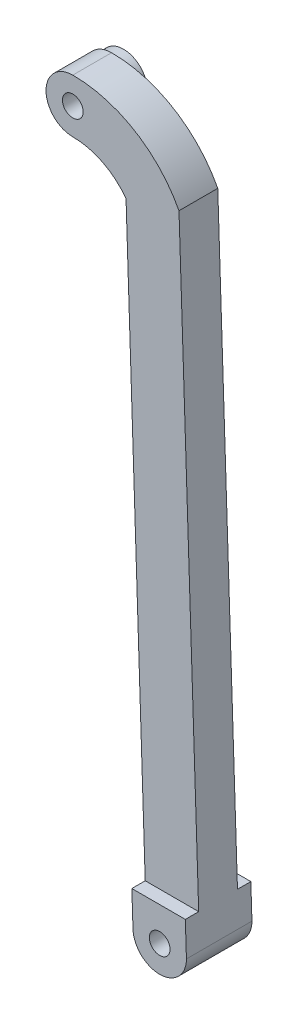
SolidWorks part; units mm, degrees
ref_plane "Plan de face" through (0, 0, 0) normal (0, 0, 1) x (1, 0, 0)
ref_plane "Plan de dessus" through (0, 0, 0) normal (0, 1, 0) x (1, 0, 0)
ref_plane "Plan de droite" through (0, 0, 0) normal (1, 0, 0) x (0, 0, -1)
sketch "Esquisse1" plane through (0, 0, 0) normal (0, 0, 1) x (1, 0, 0)
  line L2 (0, 0) -> (0, 100) construction
  line L3 (-15, 100) -> (0, 100) construction
  line L7 (-4, 0) -> (-7.0351, 91.9932)
  line L8 (4, 0) -> (0.8864, 94.3712)
  circle A14 centre (0, 0) radius 1.55
  circle A15 centre (-15, 100) radius 1.55
  arc A16 (-4, 0) -> (4, 0) centre (0, 0) ccw
  arc A17 (-15, 104) -> (-15, 96) centre (-15, 100) ccw
  arc A18 (-15, 104) -> (0.8864, 94.3712) centre (-15, 86.0802) cw
  arc A19 (-7.0351, 91.9932) -> (-15, 96) centre (-15, 86.0802) ccw
  dimension "D1" = 3.1
  dimension "D2" = 3.1
  dimension "D3" = 100
  dimension "D5" = 8
  dimension "D6" = 8
  dimension "D4" = 15
extrude "Boss.-Extru.1" add sketch "Esquisse1" along normal blind 4.9 and the other way blind 4.9 contours A19 L7 A16 L8 A18 A17 A15 A14 region at (-2.6556, 53.289, 0)
sketch "Esquisse3" plane through (0, 0, 4.9) normal (0, 0, 1) x (1, 0, 0)
  line L0 (-7.0351, 91.9932) -> (-6.2728, 68.8885)
  line L1 (-4, 0) -> (-7.0351, 91.9932) construction
  line L2 (-6.2728, 68.8885) -> (1.7272, 68.8885)
  line L3 (4, 0) -> (0.8864, 94.3712) construction
  line L4 (1.7272, 68.8885) -> (0.8864, 94.3712)
  arc A0 (-15, 96) -> (-15, 104) centre (-15, 100) cw
  arc A1 (-15, 104) -> (0.8864, 94.3712) centre (-15, 86.0802) cw
  arc A2 (-15, 96) -> (-7.0351, 91.9932) centre (-15, 86.0802) cw
extrude "Enlèv. mat.-Extru.2" [suppressed] cut sketch "Esquisse3" against normal blind 3
sketch "Sketch1" plane through (0, 0, 4.9) normal (0, 0, 1) x (1, 0, 0)
  line L0 (-7.0351, 91.9932) -> (-4.1663, 5.0408)
  line L1 (-4, 0) -> (-7.0351, 91.9932) construction
  line L2 (0.8864, 94.3712) -> (3.8337, 5.0408)
  line L3 (4, 0) -> (0.8864, 94.3712) construction
  line L4 (-4.1663, 5.0408) -> (3.8337, 5.0408)
  arc A0 (0.8864, 94.3712) -> (-15, 104) centre (-15, 86.0802) ccw
  arc A1 (0.8864, 94.3712) -> (-15, 104) centre (-15, 86.0802) ccw construction
  arc A2 (-7.0351, 91.9932) -> (-15, 96) centre (-15, 86.0802) ccw
  arc A3 (-7.0351, 91.9932) -> (-15, 96) centre (-15, 86.0802) ccw construction
  arc A5 (-15, 104) -> (-15, 96) centre (-15, 100) ccw
  point P2 (-14.8648, 96)
  point P23 (-14.8558, 103.9994)
extrude "Cut-Extrude1" cut sketch "Sketch1" against normal blind 2
mirror "Mirror1" about plane through (0, 0, 0) normal (0, 0, 1) of "Cut-Extrude1"
sketch "Sketch2" plane through (0, 0, -2.9) normal (0, 0, -1) x (-1, 0, 0)
  circle A0 centre (15, 100) radius 1.55
  circle A1 centre (15, 100) radius 3.55
  dimension "D1" = 2
extrude "Boss-Extrude1" add sketch "Sketch2" along normal blind 1.8
